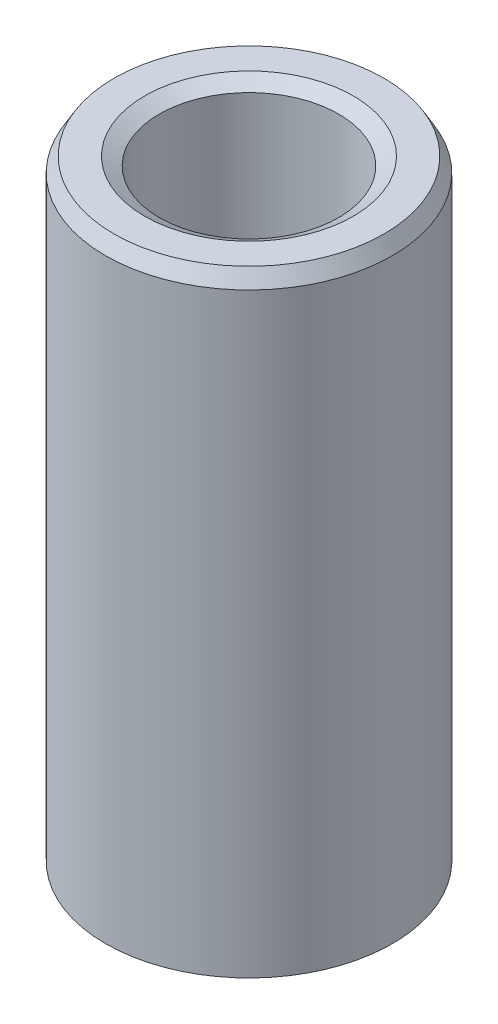
SolidWorks part; units mm, degrees
ref_plane "Front Plane" through (0, 0, 0) normal (0, 0, 1) x (1, 0, 0)
ref_plane "Top Plane" through (0, 0, 0) normal (0, 1, 0) x (1, 0, 0)
ref_plane "Right Plane" through (0, 0, 0) normal (1, 0, 0) x (0, 0, -1)
sketch "Sketch1" plane through (0, 0, 0) normal (0, 1, 0) x (1, 0, 0)
  circle A0 centre (0, 0) radius 7.5
  dimension "SLEEVE_OD" = 15
extrude "Boss-Extrude1" add sketch "Sketch1" along normal blind 32.3666
sketch "Sketch2" plane through (0, 0, 0) normal (0, 1, 0) x (1, 0, 0)
  circle A0 centre (0, 0) radius 4.6918
  dimension "BORE_D" = 9.3837
extrude "Cut-Extrude1" cut sketch "Sketch2" along normal through all
chamfer "Chamfer1" distance 0.7639 angle 30 4 edges at (0, 32.3666, 4.6918) (0, 0, 4.6918) (0, 0, 7.5) (0, 32.3666, 7.5) first distance on face at (0, 32.3666, 4.6918) first distance on face at (0, 0, 4.6918) first distance on face at (0, 32.3666, 7.5)
